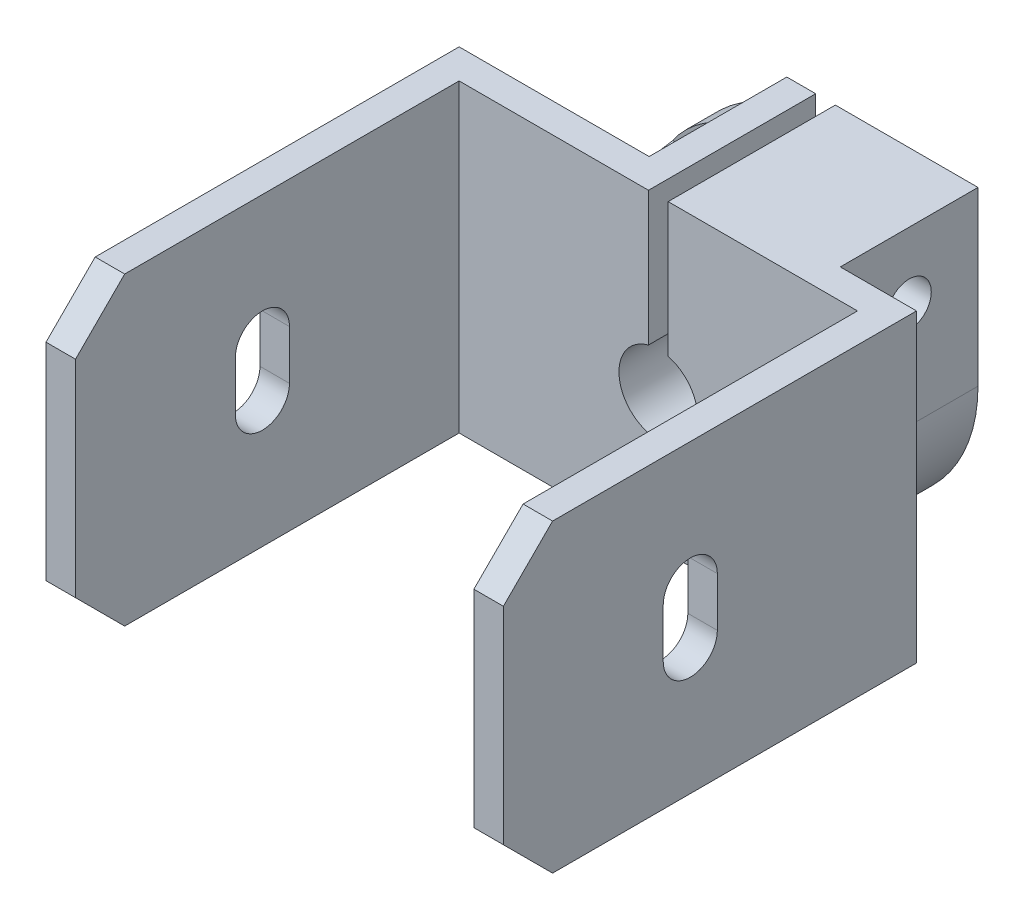
SolidWorks part; units mm, degrees
ref_plane "Front Plane" through (0, 0, 0) normal (0, 0, 1) x (1, 0, 0)
ref_plane "Top Plane" through (0, 0, 0) normal (0, 1, 0) x (1, 0, 0)
ref_plane "Right Plane" through (0, 0, 0) normal (1, 0, 0) x (0, 0, -1)
sketch "Sketch1" plane through (0, 0, 0) normal (0, 0, 1) x (1, 0, 0)
  line L0 (0, 15.5) -> (-30, 15.5)
  line L1 (-30, -15.5) -> (0, -15.5)
  line L2 (-30, 15.5) -> (-45.5, 15.5)
  line L3 (-45.5, 15.5) -> (-45.5, 0)
  line L4 (0, 15.5) -> (15.5, 15.5)
  line L5 (15.5, 15.5) -> (15.5, 0)
  circle A0 centre (0, 0) radius 4
  arc A1 (0, -15.5) -> (15.5, 0) centre (0, 0) ccw
  circle A2 centre (-30, 0) radius 2.25
  arc A3 (-45.5, 0) -> (-30, -15.5) centre (-30, 0) ccw
  dimension "D1" = 8
  dimension "D2" = 31
  dimension "D4" = 4.5
  dimension "D3" = 30
extrude "Boss-Extrude1" add sketch "Sketch1" along normal blind 24
ref_plane "Plane1" through (0, 0, -2.2) normal (0, 0, -1) x (-1, 0, 0)
sketch "Sketch2" plane through (0, 0, -2.2) normal (0, 0, -1) x (-1, 0, 0)
  line L2 (0, -15.5) -> (30, -15.5)
  line L3 (45.5, 15.5) -> (-15.5, 15.5)
  line L4 (0, -15.5) -> (30, -15.5)
  line L5 (45.5, 15.5) -> (-15.5, 15.5)
  line L7 (45.5, 0) -> (45.5, 15.5)
  line L8 (45.5, 0) -> (45.5, 15.5)
  line L10 (-15.5, 15.5) -> (-15.5, 0)
  line L11 (-15.5, 15.5) -> (-15.5, 0)
  circle A3 centre (30, 0) radius 2.25
  circle A4 centre (30, 0) radius 2.25
  circle A5 centre (0, 0) radius 4
  circle A6 centre (0, 0) radius 4
  arc A8 (-15.5, 0) -> (0, -15.5) centre (0, 0) ccw
  arc A9 (30, -15.5) -> (45.5, 0) centre (30, 0) ccw
  arc A10 (-15.5, 0) -> (0, -15.5) centre (0, 0) ccw
  arc A11 (30, -15.5) -> (45.5, 0) centre (30, 0) ccw
  dimension "D1" = 0
  dimension "D2" = 0
  dimension "D3" = 0
extrude "Boss-Extrude2" add sketch "Sketch2" along normal blind 24 separate body
sketch "Sketch3" plane through (0, 0, -26.2) normal (0, 0, -1) x (-1, 0, 0)
  line L2 (0, -15.5) -> (30, -15.5)
  line L3 (45.5, 15.5) -> (-15.5, 15.5)
  line L4 (0, -15.5) -> (30, -15.5)
  line L5 (45.5, 15.5) -> (0, 15.5)
  line L7 (45.5, 0) -> (45.5, 15.5)
  line L8 (45.5, 0) -> (45.5, 15.5)
  line L10 (-15.5, 15.5) -> (-15.5, 0)
  arc A0 (0, -15.5) -> (0, 15.5) centre (0, 0) ccw
  arc A2 (-15.5, 0) -> (0, -15.5) centre (0, 0) ccw
  arc A3 (30, -15.5) -> (45.5, 0) centre (30, 0) ccw
  arc A5 (30, -15.5) -> (45.5, 0) centre (30, 0) ccw
  dimension "D1" = 0
extrude "Cut-Extrude1" cut sketch "Sketch3" against normal blind 14
sketch "Sketch4" plane through (0, 0, 24) normal (0, 0, 1) x (1, 0, 0)
  line L2 (15.5, 15.5) -> (-45.5, 15.5)
  line L3 (-30, -15.5) -> (0, -15.5)
  line L4 (0, 15.5) -> (-45.5, 15.5)
  line L5 (-30, -15.5) -> (0, -15.5)
  line L7 (-45.5, 15.5) -> (-45.5, 0)
  line L8 (-45.5, 15.5) -> (-45.5, 0)
  line L10 (15.5, 0) -> (15.5, 15.5)
  arc A0 (0, 15.5) -> (0, -15.5) centre (0, 0) ccw
  arc A2 (0, -15.5) -> (15.5, 0) centre (0, 0) ccw
  arc A3 (-45.5, 0) -> (-30, -15.5) centre (-30, 0) ccw
  arc A5 (-45.5, 0) -> (-30, -15.5) centre (-30, 0) ccw
  dimension "D1" = 0
extrude "Cut-Extrude2" cut sketch "Sketch4" against normal blind 14
sketch "Sketch5" plane through (0, 15.5, 0) normal (0, 1, 0) x (1, 0, 0)
  line L0 (0, -10) -> (0, -24) construction
  line L1 (-45.5, 12.2) -> (0, 12.2)
  line L2 (-45.5, 12.2) -> (-45.5, 2.2)
  line L3 (-45.5, -10) -> (0, -10)
  line L4 (-45.5, 0) -> (-38.5, 0)
  line L5 (0, 12.2) -> (0, 26.2)
  line L6 (0, 26.2) -> (15.5, 26.2)
  line L7 (15.5, 26.2) -> (15.5, -24)
  line L8 (15.5, -24) -> (0, -24)
  line L9 (0, -24) -> (0, -10)
  line L10 (15.5, 0) -> (-45.5, 0) construction
  line L11 (-38.5, 0) -> (-38.5, 2.2)
  line L12 (-38.5, 2.2) -> (-45.5, 2.2)
  line L13 (-45.5, 0) -> (-45.5, -10)
  dimension "D1" = 7
extrude "Boss-Extrude3" add sketch "Sketch5" along normal blind 2
chamfer "Chamfer1" distance 10 angle 45 2 edges at (0, 15.5, 17) (0, 15.5, -19.2)
sketch "Sketch6" plane through (0, 0, -26.2) normal (0, 0, -1) x (-1, 0, 0)
  line L0 (0, 0) -> (0, 35.4054)
extrude "Cut-Extrude-Thin1" cut sketch "Sketch6" against normal blind 53 and the other way through all thin thin type mid plane wall 2
sketch "Sketch7" plane through (-1, 0, 0) normal (1, 0, 0) x (0, 0, -1)
  line L0 (26.2, 17.5) -> (12.2, 3.873) construction
  line L1 (26.2, 3.873) -> (2.2, 3.873) construction
  circle A0 centre (19.2, 10.6865) radius 2.25
  dimension "D2" = 4.5
  dimension "D1" = 14
extrude "Cut-Extrude3" cut sketch "Sketch7" against normal through all both and the other way through all
ref_plane "Plane2" through (0, 0, -1.1) normal (0, 0, -1) x (-1, 0, 0)
mirror "Mirror1" about plane through (0, 0, -1.1) normal (0, 0, -1) of "Cut-Extrude3"
sketch "Sketch8" plane through (-45.5, 0, 0) normal (-1, 0, 0) x (0, 0, 1)
  line L1 (-15.1789, 12.293) -> (-18.5807, 14.9721)
  line L2 (-18.5807, 14.9721) -> (-22.6018, 13.3656)
  line L3 (-22.6018, 13.3656) -> (-23.2211, 9.08)
  line L4 (-23.2211, 9.08) -> (-19.8193, 6.4009)
  line L5 (-19.8193, 6.4009) -> (-15.7982, 8.0073)
  line L6 (-15.7982, 8.0073) -> (-15.1789, 12.293)
  line L7 (12.9789, 12.293) -> (13.5982, 8.0073)
  line L8 (13.5982, 8.0073) -> (17.6193, 6.4009)
  line L9 (17.6193, 6.4009) -> (21.0211, 9.08)
  line L10 (21.0211, 9.08) -> (20.4018, 13.3656)
  line L11 (20.4018, 13.3656) -> (16.3807, 14.9721)
  line L12 (16.3807, 14.9721) -> (12.9789, 12.293)
  circle A0 centre (-19.2, 10.6865) radius 3.75 construction
  circle A1 centre (17, 10.6865) radius 3.75 construction
  dimension "D1" = 7.5
extrude "Cut-Extrude4" cut sketch "Sketch8" against normal blind 42
chamfer "Chamfer2" distance 1 angle 45 2 edges at (0, -4, -26.2) (0, -4, 24)
sketch "Sketch9" plane through (0, -15.5, 0) normal (0, -1, 0) x (-1, 0, 0)
  circle A0 centre (14.6024, -2.8501) radius 45.6302
extrude "Cut-Extrude5" cut sketch "Sketch9" against normal blind 2
sketch "Sketch10" plane through (0, 0, -12.2) normal (0, 0, -1) x (-1, 0, 0)
  circle A0 centre (18.9229, -1.4489) radius 89.2831
extrude "Cut-Extrude6" cut sketch "Sketch10" against normal blind 57
sketch "Sketch11" plane through (0, 0, -12.2) normal (0, 0, 1) x (1, 0, 0)
  line L0 (1, 17.5) -> (15.5, 17.5) construction
  line L1 (-20.25, 17.5) -> (20.25, 17.5)
  line L2 (-20.25, 17.5) -> (-20.25, -13.5)
  line L3 (-20.25, -13.5) -> (20.25, -13.5)
  line L4 (20.25, 17.5) -> (20.25, -13.5)
  line L5 (-7.6158, -13.5) -> (7.6158, -13.5) construction
  circle A0 centre (0, 0) radius 4
  point P0 (0, 0)
  point P12 (20.7244, 49.3982)
  point P13 (9.2137, 49.662)
  dimension "D2" = 40.5
extrude "Boss-Extrude5" add sketch "Sketch11" along normal blind 3
sketch "Sketch13" plane through (20.25, 0, 0) normal (1, 0, 0) x (0, 0, -1)
  line L0 (9.2, -13.5) -> (12.2, -13.5) construction
  line L1 (12.2, 17.5) -> (-29.8, 17.5)
  line L2 (12.2, 17.5) -> (12.2, -13.5)
  line L3 (12.2, -13.5) -> (-29.8, -13.5)
  line L4 (-29.8, 17.5) -> (-29.8, -13.5)
  dimension "D1" = 42
extrude "Boss-Extrude6" add sketch "Sketch13" along normal blind 3
sketch "Sketch14" plane through (-20.25, 0, 0) normal (-1, 0, 0) x (0, 0, 1)
  line L0 (-9.2, 17.5) -> (-12.2, 17.5) construction
  line L1 (-12.2, -13.5) -> (29.8, -13.5)
  line L2 (-12.2, -13.5) -> (-12.2, 17.5)
  line L3 (-12.2, 17.5) -> (29.8, 17.5)
  line L4 (29.8, -13.5) -> (29.8, 17.5)
  line L5 (29.8, 17.5) -> (29.8, -13.5) construction
  point P7 (-4.1953, -3.2584)
extrude "Boss-Extrude7" add sketch "Sketch14" along normal blind 3
sketch "Sketch15" plane through (20.25, 0, 0) normal (-1, 0, 0) x (0, 0, 1)
  line L0 (-9.2, 2) -> (10.8, 2) construction
  line L1 (-9.2, -13.5) -> (-9.2, 17.5) construction
  line L2 (10.8, -0.5) -> (10.8, 4.5) construction
  line L3 (8.05, -0.5) -> (8.05, 4.5)
  line L4 (13.55, -0.5) -> (13.55, 4.5)
  arc A0 (8.05, -0.5) -> (13.55, -0.5) centre (10.8, -0.5) ccw
  arc A1 (13.55, 4.5) -> (8.05, 4.5) centre (10.8, 4.5) ccw
  point P6 (10.8, 2)
  dimension "D2" = 2.75
  dimension "D1" = 20
  dimension "D3" = 5
extrude "Cut-Extrude7" cut sketch "Sketch15" against normal through all both and the other way through all
sketch "Sketch16" plane through (0, 0, -12.2) normal (0, 0, -1) x (-1, 0, 0)
  line L3 (-1, 17.5) -> (-1, 3.873)
  line L4 (1, 3.873) -> (1, 17.5)
  line L5 (1, 17.5) -> (-1, 17.5)
  line L6 (-1, 17.5) -> (-1, 3.873)
  line L7 (1, 3.873) -> (1, 17.5)
  line L8 (1, 17.5) -> (-1, 17.5)
  arc A1 (1, 3.873) -> (-1, 3.873) centre (0, 0) ccw
  arc A2 (1, 3.873) -> (-1, 3.873) centre (0, 0) ccw
  dimension "D1" = 0
extrude "Cut-Extrude8" cut sketch "Sketch16" against normal blind 18
chamfer "Chamfer4" distance 5 angle 45 4 edges at (21.75, 17.5, 29.8) (-21.75, 17.5, 29.8) (-21.75, -13.5, 29.8) (21.75, -13.5, 29.8)
